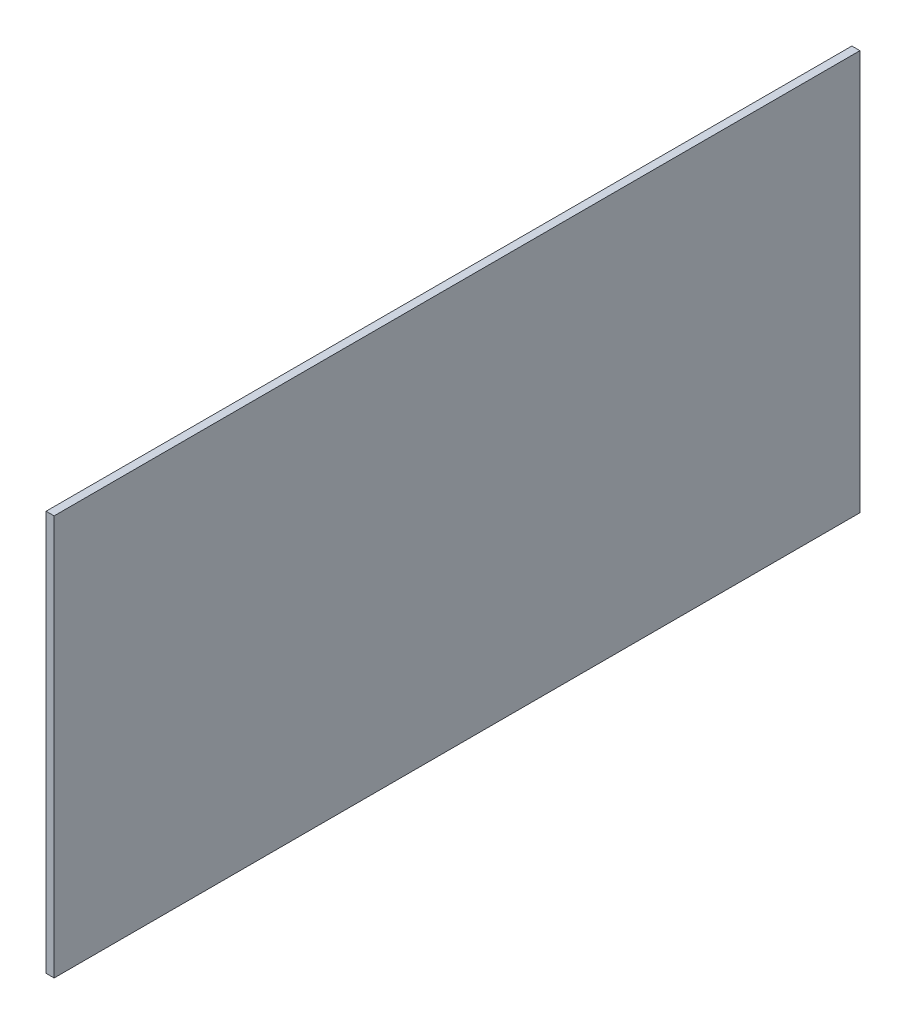
SolidWorks part; units mm, degrees
material "AISI 304"
ref_plane "Спереди" through (0, 0, 0) normal (0, 0, 1) x (1, 0, 0)
ref_plane "Сверху" through (0, 0, 0) normal (0, 1, 0) x (1, 0, 0)
ref_plane "Справа" through (0, 0, 0) normal (1, 0, 0) x (0, 0, -1)
sketch "Эскиз1" plane through (0, 0, 0) normal (1, 0, 0) x (0, 0, -1)
  line L1 (-150, 74.5) -> (150, 74.5)
  line L2 (-150, 74.5) -> (-150, -74.5)
  line L3 (-150, -74.5) -> (150, -74.5)
  line L4 (150, 74.5) -> (150, -74.5)
  line L5 (-150, 74.5) -> (150, -74.5) construction
  line L6 (-150, -74.5) -> (150, 74.5) construction
  point P0 (0, 0)
  dimension "D1" = 300
  dimension "D2" = 149
base flange "Базовая кромка1" sketch "Эскиз1" thickness 3 reverse thickness direction no parameters "D1"=4
sketch "Сгиб-Линии1" plane through (0, 0, 0) normal (0, 1, 0) x (1, 0, 0)
sketch "Граничная рамка1" plane through (0, 0, 0) normal (0, 1, 0) x (1, 0, 0)
sheet metal parameters "Листовой металл3" thickness 3 parameters "D1"=4
flat pattern "Развертка3" [suppressed]
sketch "Сгиб-Линии2" plane through (0, 0, 0) normal (0, 1, 0) x (1, 0, 0)
sketch "Граничная рамка2" [suppressed] plane through (0, 0, 0) normal (0, 1, 0) x (1, 0, 0)
